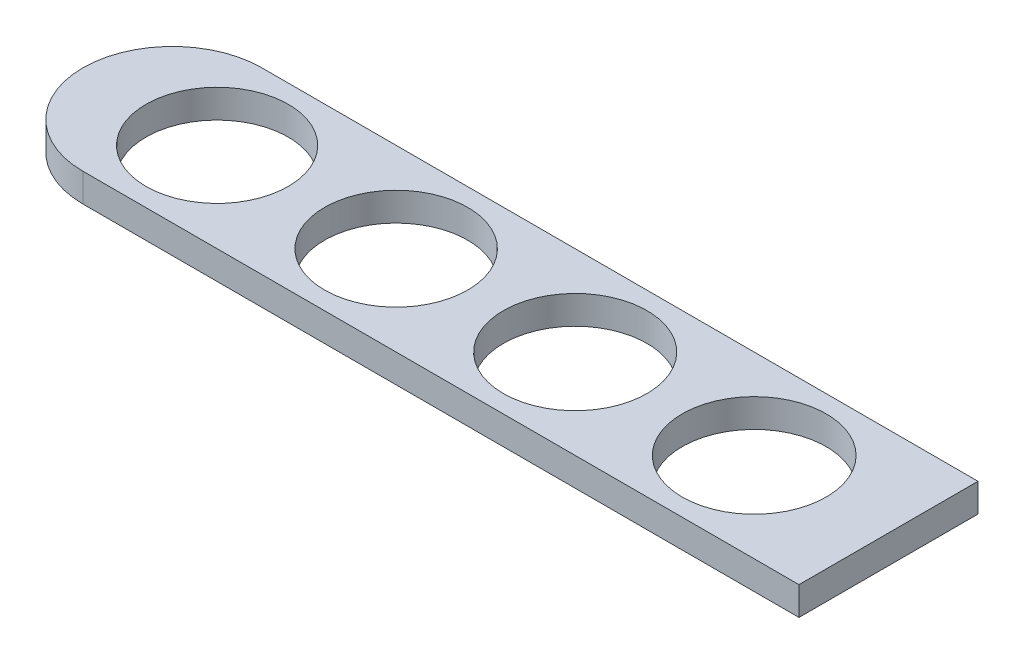
SolidWorks part; units mm, degrees
ref_plane "Front Plane" through (0, 0, 0) normal (0, 0, 1) x (1, 0, 0)
ref_plane "Top Plane" through (0, 0, 0) normal (0, 1, 0) x (1, 0, 0)
ref_plane "Right Plane" through (0, 0, 0) normal (1, 0, 0) x (0, 0, -1)
sketch "Sketch1" plane through (0, 0, 0) normal (0, 1, 0) x (1, 0, 0)
  line L0 (-45, 0) -> (45, 0) construction
  line L1 (-45, 10) -> (45, 10)
  line L2 (-45, 10) -> (-45, -10)
  line L3 (-45, -10) -> (45, -10)
  line L4 (45, 10) -> (45, -10)
  line L5 (-45, 10) -> (45, -10) construction
  line L6 (-45, -10) -> (45, 10) construction
  circle A0 centre (-30, 0) radius 7.95
  circle A2 centre (-10, 0) radius 8
  circle A3 centre (10, 0) radius 8.025
  circle A4 centre (30, 0) radius 8.05
  point P0 (0, 0)
  dimension "D3" = 15.9
  dimension "D4" = 16
  dimension "D5" = 16.05
  dimension "D6" = 16.1
  dimension "D1" = 90
  dimension "D2" = 20
  dimension "D7" = 20
  dimension "D8" = 20
  dimension "D9" = 20
  dimension "D10" = 15
extrude "Boss-Extrude1" add sketch "Sketch1" along normal blind 3.175
fillet "Fillet1" radius 10 2 edges at (-45, 1.5875, -10) (-45, 1.5875, 10)
